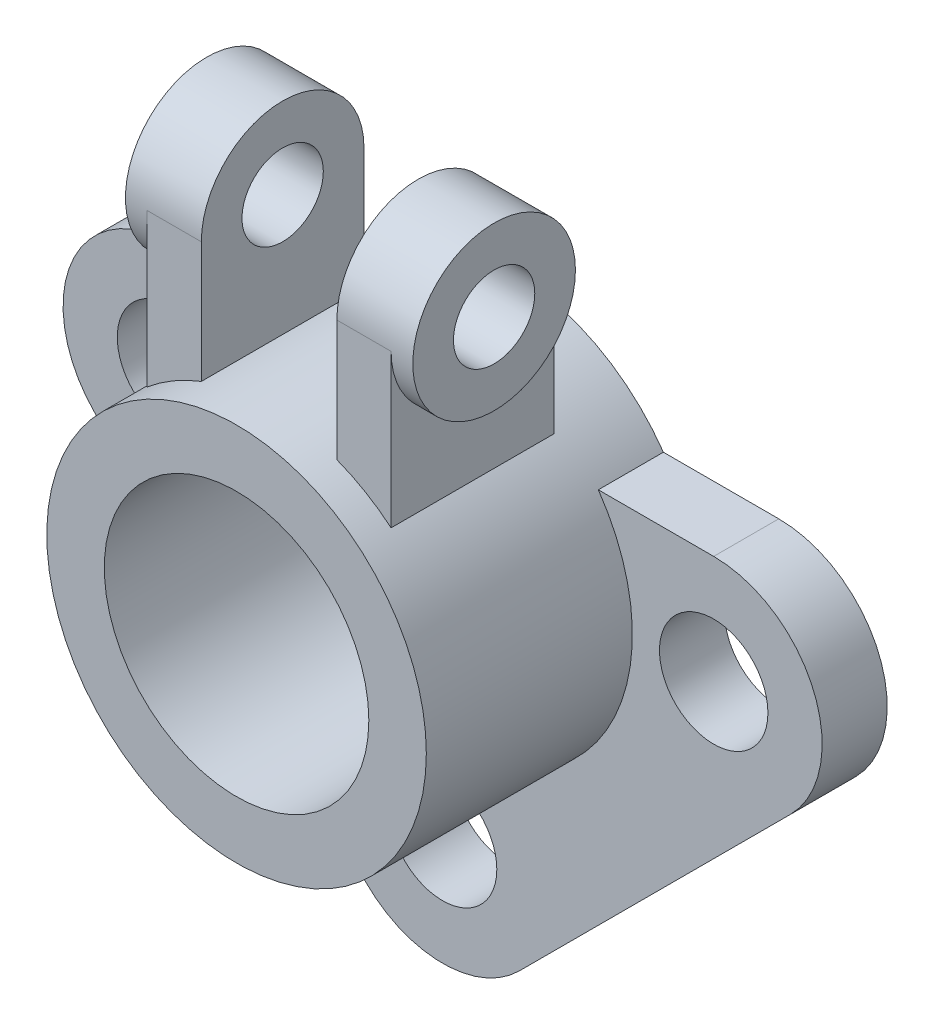
SolidWorks part; units mm, degrees
material "2014 Alloy"
ref_plane "Front Plane" through (0, 0, 0) normal (0, 0, 1) x (1, 0, 0)
ref_plane "Top Plane" through (0, 0, 0) normal (0, 1, 0) x (1, 0, 0)
ref_plane "Right Plane" through (0, 0, 0) normal (1, 0, 0) x (0, 0, -1)
sketch "Sketch1" plane through (0, 0, 0) normal (0, 0, 1) x (1, 0, 0)
  line L0 (0, 0) -> (0, 55) construction
  line L1 (0, 0) -> (0, -50) construction
  line L2 (-50, 20) -> (50, 20)
  line L3 (64.1421, -14.1421) -> (14.1421, -64.1421)
  line L4 (-14.1421, -64.1421) -> (-64.1421, -14.1421)
  arc A0 (50, 20) -> (64.1421, -14.1421) centre (50, 0) cw
  arc A1 (-50, 20) -> (-64.1421, -14.1421) centre (-50, 0) ccw
  arc A2 (14.1421, -64.1421) -> (-14.1421, -64.1421) centre (0, -50) cw
  circle A3 centre (-50, 0) radius 10
  circle A4 centre (50, 0) radius 10
  circle A5 centre (0, -50) radius 10
  circle A6 centre (0, 0) radius 35
  circle A7 centre (0, 0) radius 24.3968
  point P6 (0, 20)
  point P19 (0, 0)
  dimension "D3" = 20
  dimension "D4" = 20
  dimension "D5" = 20
  dimension "D6" = 20
  dimension "D8" = 70
  dimension "D1" = 50
  dimension "D2" = 55
  dimension "D7" = 100
extrude "Boss-Extrude1" add sketch "Sketch1" along normal blind 12 contours A6 L2 A1 L4 A2 L3 A0 A5 A4 A3 region at (-39.3614, 18.3357, 0)
extrude "Boss-Extrude2" add sketch "Sketch1<3>" along normal blind 50 contours A7 L2 A6 | A7 L2 A6 | A6 | A7 region at (0, 26.8234, 0) region at (-21.3471, 19.1098, 0)
sketch "Sketch1<3>" plane through (0, 0, 0) normal (0, 0, 1) x (1, 0, 0) same geometry as "Sketch1"
sketch "Sketch2" plane through (0, 0, 0) normal (1, 0, 0) x (0, 0, -1)
  line L0 (-50, 35) -> (-44, 35) construction
  line L1 (0, 35) -> (-50, 35) construction
  line L2 (-44, 35) -> (-44, 26.043)
  line L3 (-44, 26.043) -> (-14, 26.043)
  line L4 (-14, 26.043) -> (-14, 55)
  line L5 (-14, 55) -> (-44, 55)
  line L6 (-44, 55) -> (-44, 35)
  dimension "D1" = 6
  dimension "D2" = 30
  dimension "D3" = 55
extrude "Boss-Extrude3" add sketch "Sketch2" along normal blind 10 from offset 12.5
sketch "Sketch3" plane through (22.5, 0, 0) normal (1, 0, 0) x (0, 0, -1)
  line L0 (-14, 55) -> (-44, 55) construction
  circle A0 centre (-29, 55) radius 15
extrude "Boss-Extrude4" add sketch "Sketch3" along normal blind 4 and the other way blind 10
sketch "Sketch4" plane through (26.5, 0, 0) normal (1, 0, 0) x (0, 0, -1)
  circle A0 centre (-29, 55) radius 7.5
  dimension "D1" = 15
extrude "Cut-Extrude1" cut sketch "Sketch4" against normal through all
mirror "Mirror1" about plane through (0, 0, 0) normal (1, 0, 0) of bodies 105
